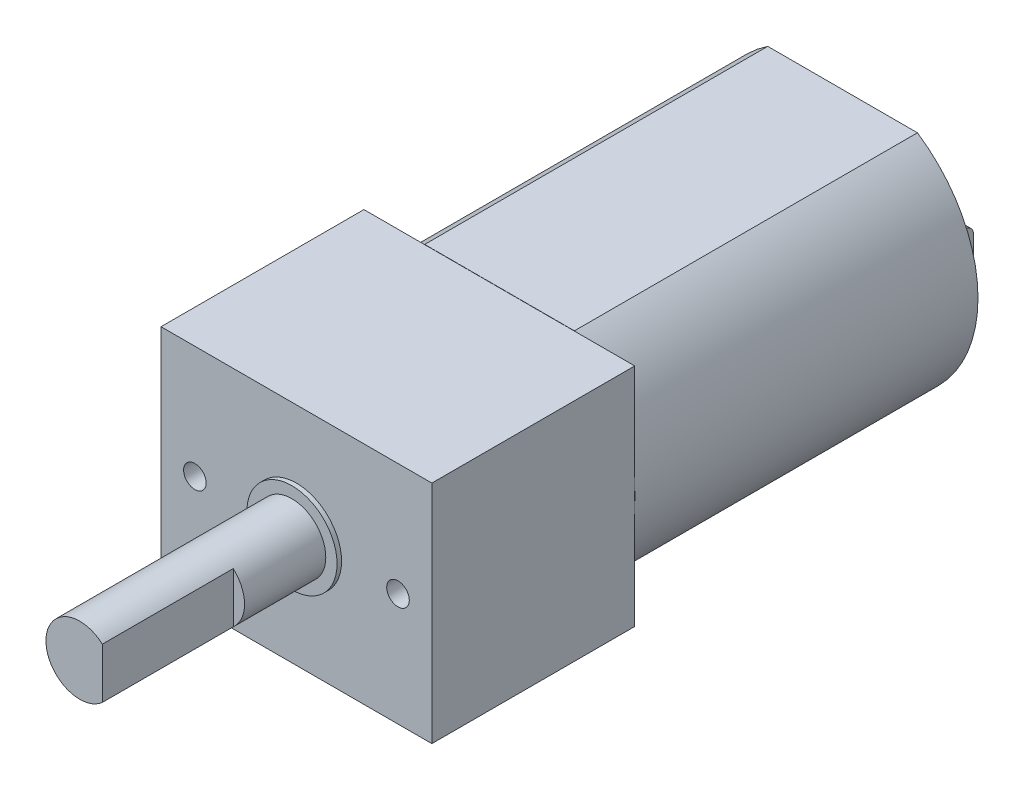
SolidWorks part; units mm, degrees
ref_plane "前视基准面" through (0, 0, 0) normal (0, 0, 1) x (1, 0, 0)
ref_plane "上视基准面" through (0, 0, 0) normal (0, 1, 0) x (1, 0, 0)
ref_plane "右视基准面" through (0, 0, 0) normal (1, 0, 0) x (0, 0, -1)
other "Configuration Table"
sketch "草图1" plane through (0, 0, 0) normal (0, 0, 1) x (1, 0, 0)
  line L0 (3.5, -0.75) -> (3.8, -0.75)
  line L1 (-6, -5) -> (6, -5)
  line L2 (-6, -5) -> (-6, 5)
  line L3 (-6, 5) -> (6, 5)
  line L4 (6, -5) -> (6, 5)
  line L5 (-6, -5) -> (6, 5) construction
  line L6 (-6, 5) -> (6, -5) construction
  line L7 (-3.8, -0.75) -> (-3.5, -0.75)
  line L8 (-3.8, -0.75) -> (-3.8, 0.75)
  line L9 (-3.8, 0.75) -> (-3.5, 0.75)
  line L10 (-3.5, -0.75) -> (-3.5, 0.75)
  line L11 (-3.8, -0.75) -> (-3.5, 0.75) construction
  line L12 (-3.8, 0.75) -> (-3.5, -0.75) construction
  line L13 (3.5, -0.75) -> (3.5, 0.75)
  line L14 (3.5, 0.75) -> (3.8, 0.75)
  line L15 (3.8, -0.75) -> (3.8, 0.75)
  line L16 (-3.5, 0) -> (3.5, 0) construction
  circle A0 centre (0, 0) radius 6
  circle A1 centre (0, 0) radius 2.5
  circle A2 centre (0, 0) radius 1.5
  point P0 (0, 0)
  point P8 (-3.65, 0)
  dimension "D6" = 5
  dimension "D7" = 3
  dimension "D1" = 12
  dimension "D2" = 10
  dimension "D3" = 0.3
  dimension "D4" = 1.5
  dimension "D5" = 7
extrude "凸台-拉伸1" add sketch "草图1" along normal blind 15.2 contours L3 A0 L1 A1 L15 L0 L13 L14 L10 L7 L8 L9 | A1 A2 | A2 | L0 L15 L14 L13 | L7 L10 L9 L8 region at (3.65, 0, 0) region at (-5.1491, -2.7634, 0) region at (-3.65, 0, 0) region at (-2.4293, 0, 0) region at (0, 0, 0)
extrude "凸台-拉伸2" add sketch "草图1<4>" against normal blind 2 contours L13 L14 L15 L0 | L8 L9 L10 L7
sketch "草图1<4>" plane through (0, 0, 0) normal (0, 0, 1) x (1, 0, 0) same geometry as "草图1"
sketch "草图2" plane through (3.8, 0, 0) normal (1, 0, 0) x (0, 0, -1)
  line L0 (0.95, 0) -> (1.05, 0) construction
  line L1 (0.95, 0.45) -> (1.05, 0.45)
  line L2 (0.95, -0.45) -> (1.05, -0.45)
  line L4 (1, 0.75) -> (1, -0.75) construction
  line L5 (2, 0.75) -> (0, 0.75) construction
  line L6 (2, -0.75) -> (0, -0.75) construction
  arc A0 (0.95, 0.45) -> (0.95, -0.45) centre (0.95, 0) ccw
  arc A1 (1.05, -0.45) -> (1.05, 0.45) centre (1.05, 0) ccw
  point P3 (1, 0)
  dimension "D2" = 0.45
  dimension "D1" = 0.1
extrude "切除-拉伸2" cut sketch "草图2" against normal through all
fillet "圆角1" radius 0.4 4 edges at (-3.65, 0.75, -2) (-3.65, -0.75, -2) (3.65, 0.75, -2) (3.65, -0.75, -2)
extrude "凸台-拉伸3" add sketch "草图1<5>" against normal blind 1.2 contours A1 A2 | A2 region at (-2.4293, 0, 0) region at (0, 0, 0)
sketch "草图1<5>" plane through (0, 0, 0) normal (0, 0, 1) x (1, 0, 0) same geometry as "草图1"
extrude "切除-拉伸1" cut sketch "草图1<7>" along normal blind 0.6 from surface contours A2 region at (0, 0, 0) starting at face at (2.5, 0, -1.2)
sketch "草图1<7>" plane through (0, 0, 0) normal (0, 0, 1) x (1, 0, 0) same geometry as "草图1"
fillet "圆角2" radius 0.4 1 edges at (2.5, 0, -1.2)
sketch "草图3" plane through (0, 0, 15.2) normal (0, 0, 1) x (1, 0, 0)
  circle A0 centre (0, 0) radius 2
  circle A1 centre (0, 0) radius 0.5
  dimension "D1" = 4
  dimension "D2" = 1
extrude "凸台-拉伸4" add sketch "草图3" along normal blind 0.5 contours A0
extrude "凸台-拉伸5" add sketch "草图3<3>" along normal blind 3 contours A1 region at (0, 0, 15.2)
sketch "草图3<3>" plane through (0, 0, 15.2) normal (0, 0, 1) x (1, 0, 0) same geometry as "草图3"
sketch "草图4" plane through (0, 0, 15.2) normal (0, 0, 1) x (1, 0, 0)
  line L0 (-4.25, 0) -> (4.25, 0) construction
  line L1 (0, 0) -> (0, 5) construction
  line L2 (-3.3166, 5) -> (3.3166, 5) construction
  circle A0 centre (-4.25, 0) radius 0.7
  circle A1 centre (4.25, 0) radius 0.7
  circle A2 centre (0, 3.5) radius 0.5
  dimension "D1" = 1.4
  dimension "D2" = 8.5
  dimension "D3" = 1
  dimension "D4" = 3.5
extrude "切除-拉伸3" cut sketch "草图4" against normal blind 1
sketch "草图5" plane through (0, 0, 15.2) normal (0, 0, 1) x (1, 0, 0)
  line L1 (-6, -5) -> (6, -5)
  line L2 (-6, -5) -> (-6, 5)
  line L3 (-6, 5) -> (6, 5)
  line L4 (6, -5) -> (6, 5)
  line L5 (-6, -5) -> (6, 5) construction
  line L6 (-6, 5) -> (6, -5) construction
  point P0 (0, 0)
  dimension "D1" = 12
  dimension "D2" = 10
extrude "凸台-拉伸6" add sketch "草图5" along normal blind 8.99 from offset 0.01 contours L2 L3 L4 L1
sketch "草图6" plane through (0, 0, 24.2) normal (0, 0, 1) x (1, 0, 0)
  line L0 (1, 1.118) -> (1, -1.118)
  circle A0 centre (0, 0) radius 2
  circle A1 centre (0, 0) radius 1.5
  dimension "D2" = 4
  dimension "D3" = 3
  dimension "D1" = 1
extrude "凸台-拉伸7" add sketch "草图6" along normal blind 0.2 contours A0
extrude "凸台-拉伸8" add sketch "草图6<4>" along normal blind 3.8 contours A1
sketch "草图6<4>" plane through (0, 0, 24.2) normal (0, 0, 1) x (1, 0, 0) same geometry as "草图6"
extrude "凸台-拉伸9" add sketch "草图6<5>" along normal blind 5.8 from surface contours L0 A1 region at (-0.148, 0, 24.2) starting at face at (1.5, 0, 28)
sketch "草图6<5>" plane through (0, 0, 24.2) normal (0, 0, 1) x (1, 0, 0) same geometry as "草图6"
sketch "草图7" plane through (0, 0, 24.2) normal (0, 0, 1) x (1, 0, 0)
  line L0 (-4.5, 0) -> (4.5, 0) construction
  circle A0 centre (-4.5, 0) radius 0.5
  circle A1 centre (4.5, 0) radius 0.5
  dimension "D2" = 1
  dimension "D3" = 1
  dimension "D1" = 9
extrude "切除-拉伸5" cut sketch "草图7" against normal blind 5.8 contours A0 | A1
